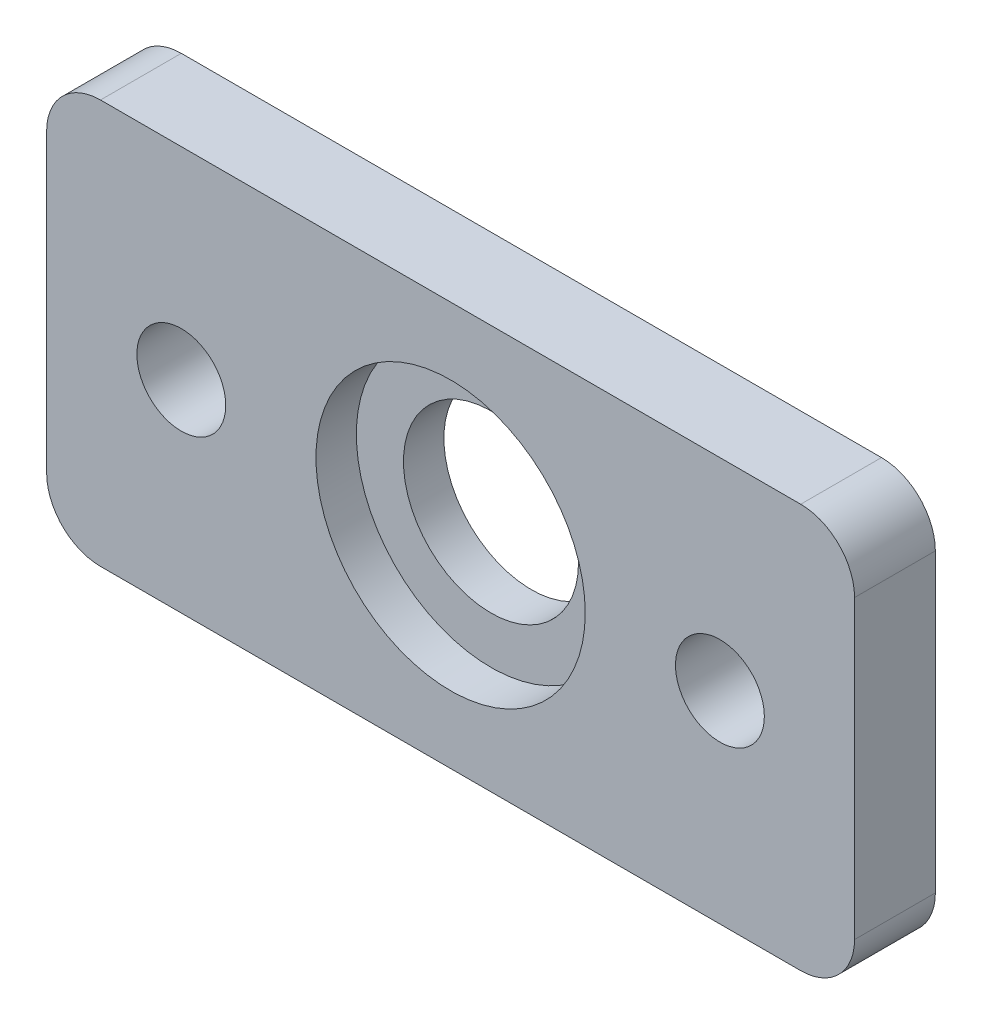
SolidWorks part; units mm, degrees
ref_plane "Спереди" through (0, 0, 0) normal (0, 0, 1) x (1, 0, 0)
ref_plane "Сверху" through (0, 0, 0) normal (0, 1, 0) x (1, 0, 0)
ref_plane "Справа" through (0, 0, 0) normal (1, 0, 0) x (0, 0, -1)
sketch "Эскиз1" plane through (0, 0, 0) normal (0, 0, 1) x (1, 0, 0)
  line L1 (2, 0) -> (28, 0)
  line L2 (0, 2) -> (0, 13)
  line L3 (2, 15) -> (28, 15)
  line L4 (30, 2) -> (30, 13)
  arc A0 (28, 15) -> (30, 13) centre (28, 13) cw
  arc A1 (28, 0) -> (30, 2) centre (28, 2) ccw
  arc A2 (2, 0) -> (0, 2) centre (2, 2) cw
  arc A3 (0, 13) -> (2, 15) centre (2, 13) cw
  point P9 (30, 0)
  point P12 (0, 0)
  point P15 (0, 15)
  dimension "D3" = 2
  dimension "D1" = 30
  dimension "D2" = 15
extrude "Бобышка-Вытянуть1" add sketch "Эскиз1" along normal blind 3
sketch "Эскиз2" plane through (0, 0, 3) normal (0, 0, 1) x (1, 0, 0)
  line L0 (28, 15) -> (2, 15) construction
  line L1 (30, 2) -> (30, 13) construction
  circle A0 centre (15, 7.5) radius 5
  point P4 (15, 15)
  point P7 (30, 7.5)
  dimension "D1" = 10
  dimension "D2" = 0
  dimension "D3" = 0
extrude "Вырез-Вытянуть1" cut sketch "Эскиз2" against normal blind 1.5
sketch "Эскиз3" plane through (0, 0, 3) normal (0, 0, 1) x (1, 0, 0)
  circle A0 centre (15, 7.5) radius 3.25
  dimension "D1" = 6.5
extrude "Вырез-Вытянуть2" cut sketch "Эскиз3" against normal through all
sketch "Эскиз4" plane through (0, 0, 3) normal (0, 0, 1) x (1, 0, 0)
  line L0 (0, 13) -> (0, 2) construction
  circle A0 centre (5, 7.5) radius 1.65
  circle A1 centre (15, 7.5) radius 3.25 construction
  circle A2 centre (25, 7.5) radius 1.65
  point P4 (0, 7.5)
  dimension "D1" = 3.3
  dimension "D2" = 0
  dimension "D3" = 10
  dimension "D4" = 2
extrude "Вырез-Вытянуть3" cut sketch "Эскиз4" against normal through all
